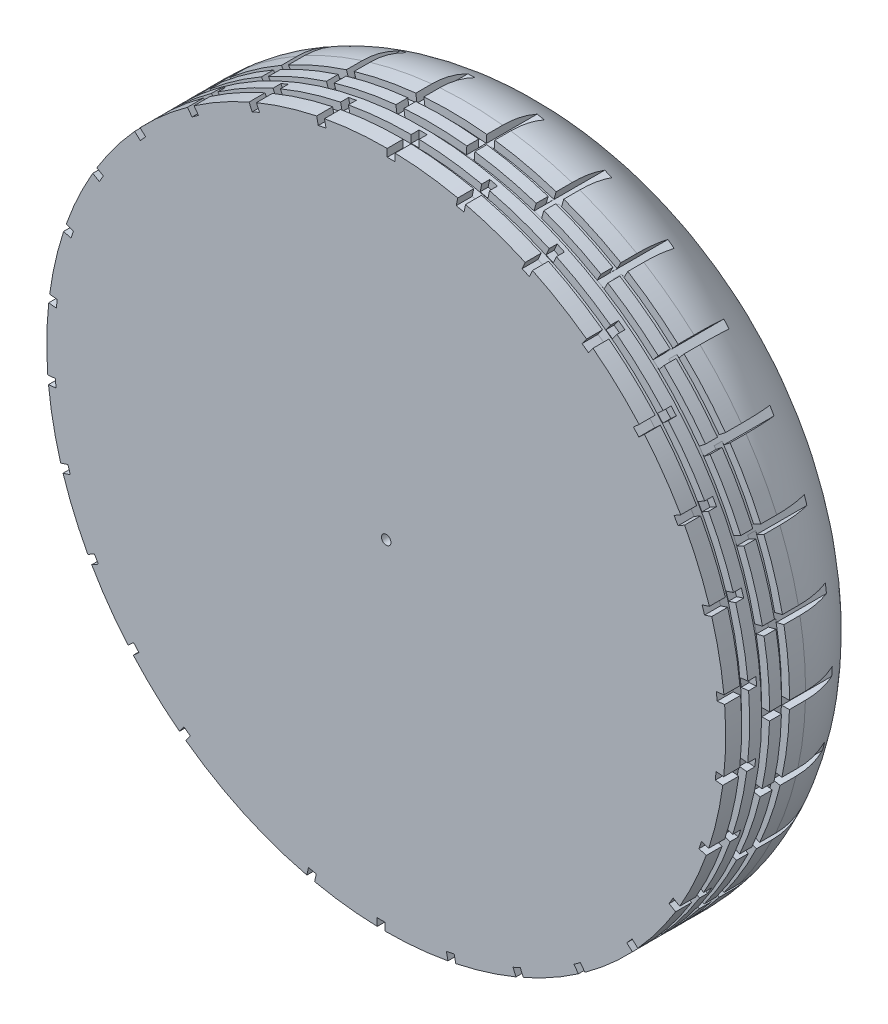
SolidWorks part; units mm, degrees
material "BUTYL"
ref_plane "Front Plane" through (0, 0, 0) normal (0, 0, 1) x (1, 0, 0)
ref_plane "Top Plane" through (0, 0, 0) normal (0, 1, 0) x (1, 0, 0)
ref_plane "Right Plane" through (0, 0, 0) normal (1, 0, 0) x (0, 0, -1)
sketch "Sketch1" plane through (0, 0, 0) normal (0, 0, 1) x (1, 0, 0)
  circle A0 centre (0, 0) radius 107.95
  dimension "D1" = 215.9
extrude "Boss-Extrude1" add sketch "Sketch1" along normal blind 25.4
sketch "Sketch3" plane through (0, 0, 0) normal (0, 1, 0) x (1, 0, 0)
  line L0 (107.95, 0) -> (-107.95, 0) construction
  line L1 (-107.95, 0) -> (107.95, 0)
  line L2 (0, 50.8) -> (0, 0) construction
  ellipse E0 centre (0, 0) end of major axis (107.95, 0) minor radius 50.8 (107.95, 0) -> (-107.95, 0) ccw
revolve "Revolve1" add sketch "Sketch3" angle 360 about L2 region at (0, 0, -21.5559)
sketch "Sketch5" plane through (0, 0, 25.4) normal (0, 0, 1) x (1, 0, 0)
  circle A0 centre (0, 0) radius 1.5
  dimension "D1" = 3
extrude "Cut-Extrude1" cut sketch "Sketch5" against normal blind 50.8
ref_plane "Plane1" through (0, 0, 12.7) normal (0, 0, 1) x (1, 0, 0)
sketch "Sketch6" plane through (0, 0, 12.7) normal (0, 0, 1) x (1, 0, 0)
  circle A0 centre (0, 0) radius 107.95
  circle A1 centre (0, 0) radius 105.41
  dimension "D1" = 210.82
extrude "Cut-Extrude2" cut sketch "Sketch6" against normal mid plane 2.54
pattern_linear "LPattern1" count 2 spacing 6.35 along (0, 0, 1) count 2 spacing 6.35 along (0, 0, -1) of "Cut-Extrude2" pattern seed only yes
sketch "Sketch9" plane through (0, 0, 12.7) normal (0, 0, 1) x (1, 0, 0)
  line L0 (25.2624, 105.0942) -> (24.7344, 102.6097)
  line L1 (0, 105.51) -> (0.3201, 105.51) construction
  line L2 (0.3201, 105.51) -> (2.8601, 105.51)
  line L3 (0.3201, 105.51) -> (0.3201, 108.05)
  line L4 (0.3201, 108.05) -> (2.8601, 108.05)
  line L5 (2.8601, 108.05) -> (2.8601, 105.51)
  line L6 (22.2499, 103.1378) -> (24.7344, 102.6097)
  line L7 (22.2499, 103.1378) -> (22.778, 105.6223)
  line L8 (22.778, 105.6223) -> (25.2624, 105.0942)
  line L9 (46.5607, 97.5453) -> (45.5276, 95.2249)
  line L10 (43.2072, 96.258) -> (45.5276, 95.2249)
  line L11 (43.2072, 96.258) -> (44.2403, 98.5784)
  line L12 (44.2403, 98.5784) -> (46.5607, 97.5453)
  line L13 (65.8241, 85.7332) -> (64.3311, 83.6783)
  line L14 (62.2762, 85.1712) -> (64.3311, 83.6783)
  line L15 (62.2762, 85.1712) -> (63.7692, 87.2261)
  line L16 (63.7692, 87.2261) -> (65.8241, 85.7332)
  line L17 (82.2106, 70.1741) -> (80.323, 68.4745)
  line L18 (78.6234, 70.3621) -> (80.323, 68.4745)
  line L19 (78.6234, 70.3621) -> (80.511, 72.0617)
  line L20 (80.511, 72.0617) -> (82.2106, 70.1741)
  line L21 (95.0041, 51.5481) -> (92.8044, 50.2781)
  line L22 (91.5344, 52.4778) -> (92.8044, 50.2781)
  line L23 (91.5344, 52.4778) -> (93.7341, 53.7478)
  line L24 (93.7341, 53.7478) -> (95.0041, 51.5481)
  line L25 (103.6455, 30.6692) -> (101.2298, 29.8843)
  line L26 (100.4449, 32.3) -> (101.2298, 29.8843)
  line L27 (100.4449, 32.3) -> (102.8606, 33.0849)
  line L28 (102.8606, 33.0849) -> (103.6455, 30.6692)
  line L29 (107.7571, 8.4499) -> (105.231, 8.1844)
  line L30 (104.9655, 10.7105) -> (105.231, 8.1844)
  line L31 (104.9655, 10.7105) -> (107.4916, 10.976)
  line L32 (107.4916, 10.976) -> (107.7571, 8.4499)
  line L33 (107.1591, -14.1387) -> (104.6331, -13.8732)
  line L34 (104.8986, -11.3471) -> (104.6331, -13.8732)
  line L35 (104.8986, -11.3471) -> (107.4246, -11.6126)
  line L36 (107.4246, -11.6126) -> (107.1591, -14.1387)
  line L37 (101.8778, -36.1094) -> (99.4622, -35.3245)
  line L38 (100.2471, -32.9088) -> (99.4622, -35.3245)
  line L39 (100.2471, -32.9088) -> (102.6628, -33.6937)
  line L40 (102.6628, -33.6937) -> (101.8778, -36.1094)
  line L41 (92.144, -56.5019) -> (89.9443, -55.2319)
  line L42 (91.2143, -53.0322) -> (89.9443, -55.2319)
  line L43 (91.2143, -53.0322) -> (93.414, -54.3022)
  line L44 (93.414, -54.3022) -> (92.144, -56.5019)
  line L45 (78.383, -74.425) -> (76.4954, -72.7254)
  line L46 (78.195, -70.8378) -> (76.4954, -72.7254)
  line L47 (78.195, -70.8378) -> (80.0826, -72.5374)
  line L48 (80.0826, -72.5374) -> (78.383, -74.425)
  line L49 (61.1963, -89.0954) -> (59.7034, -87.0405)
  line L50 (61.7583, -85.5475) -> (59.7034, -87.0405)
  line L51 (61.7583, -85.5475) -> (63.2512, -87.6024)
  line L52 (63.2512, -87.6024) -> (61.1963, -89.0954)
  line L53 (41.3351, -99.8719) -> (40.302, -97.5515)
  line L54 (42.6224, -96.5184) -> (40.302, -97.5515)
  line L55 (42.6224, -96.5184) -> (43.6555, -98.8388)
  line L56 (43.6555, -98.8388) -> (41.3351, -99.8719)
  line L57 (19.6673, -106.2835) -> (19.1392, -103.799)
  line L58 (21.6237, -103.2709) -> (19.1392, -103.799)
  line L59 (21.6237, -103.2709) -> (22.1518, -105.7554)
  line L60 (22.1518, -105.7554) -> (19.6673, -106.2835)
  line L61 (-2.8601, -108.05) -> (-2.8601, -105.51)
  line L62 (-0.3201, -105.51) -> (-2.8601, -105.51)
  line L63 (-0.3201, -105.51) -> (-0.3201, -108.05)
  line L64 (-0.3201, -108.05) -> (-2.8601, -108.05)
  line L65 (-25.2624, -105.0942) -> (-24.7344, -102.6097)
  line L66 (-22.2499, -103.1378) -> (-24.7344, -102.6097)
  line L67 (-22.2499, -103.1378) -> (-22.778, -105.6223)
  line L68 (-22.778, -105.6223) -> (-25.2624, -105.0942)
  line L69 (-46.5607, -97.5453) -> (-45.5276, -95.2249)
  line L70 (-43.2072, -96.258) -> (-45.5276, -95.2249)
  line L71 (-43.2072, -96.258) -> (-44.2403, -98.5784)
  line L72 (-44.2403, -98.5784) -> (-46.5607, -97.5453)
  line L73 (-65.8241, -85.7332) -> (-64.3311, -83.6783)
  line L74 (-62.2762, -85.1712) -> (-64.3311, -83.6783)
  line L75 (-62.2762, -85.1712) -> (-63.7692, -87.2261)
  line L76 (-63.7692, -87.2261) -> (-65.8241, -85.7332)
  line L77 (-82.2106, -70.1741) -> (-80.323, -68.4745)
  line L78 (-78.6234, -70.3621) -> (-80.323, -68.4745)
  line L79 (-78.6234, -70.3621) -> (-80.511, -72.0617)
  line L80 (-80.511, -72.0617) -> (-82.2106, -70.1741)
  line L81 (-95.0041, -51.5481) -> (-92.8044, -50.2781)
  line L82 (-91.5344, -52.4778) -> (-92.8044, -50.2781)
  line L83 (-91.5344, -52.4778) -> (-93.7341, -53.7478)
  line L84 (-93.7341, -53.7478) -> (-95.0041, -51.5481)
  line L85 (-103.6455, -30.6692) -> (-101.2298, -29.8843)
  line L86 (-100.4449, -32.3) -> (-101.2298, -29.8843)
  line L87 (-100.4449, -32.3) -> (-102.8606, -33.0849)
  line L88 (-102.8606, -33.0849) -> (-103.6455, -30.6692)
  line L89 (-107.7571, -8.4499) -> (-105.231, -8.1844)
  line L90 (-104.9655, -10.7105) -> (-105.231, -8.1844)
  line L91 (-104.9655, -10.7105) -> (-107.4916, -10.976)
  line L92 (-107.4916, -10.976) -> (-107.7571, -8.4499)
  line L93 (-107.1591, 14.1387) -> (-104.6331, 13.8732)
  line L94 (-104.8986, 11.3471) -> (-104.6331, 13.8732)
  line L95 (-104.8986, 11.3471) -> (-107.4246, 11.6126)
  line L96 (-107.4246, 11.6126) -> (-107.1591, 14.1387)
  line L97 (-101.8778, 36.1094) -> (-99.4622, 35.3245)
  line L98 (-100.2471, 32.9088) -> (-99.4622, 35.3245)
  line L99 (-100.2471, 32.9088) -> (-102.6628, 33.6937)
  line L100 (-102.6628, 33.6937) -> (-101.8778, 36.1094)
  line L101 (-92.144, 56.5019) -> (-89.9443, 55.2319)
  line L102 (-91.2143, 53.0322) -> (-89.9443, 55.2319)
  line L103 (-91.2143, 53.0322) -> (-93.414, 54.3022)
  line L104 (-93.414, 54.3022) -> (-92.144, 56.5019)
  line L105 (-78.383, 74.425) -> (-76.4954, 72.7254)
  line L106 (-78.195, 70.8378) -> (-76.4954, 72.7254)
  line L107 (-78.195, 70.8378) -> (-80.0826, 72.5374)
  line L108 (-80.0826, 72.5374) -> (-78.383, 74.425)
  line L109 (-61.1963, 89.0954) -> (-59.7034, 87.0405)
  line L110 (-61.7583, 85.5475) -> (-59.7034, 87.0405)
  line L111 (-61.7583, 85.5475) -> (-63.2512, 87.6024)
  line L112 (-63.2512, 87.6024) -> (-61.1963, 89.0954)
  line L113 (-41.3351, 99.8719) -> (-40.302, 97.5515)
  line L114 (-42.6224, 96.5184) -> (-40.302, 97.5515)
  line L115 (-42.6224, 96.5184) -> (-43.6555, 98.8388)
  line L116 (-43.6555, 98.8388) -> (-41.3351, 99.8719)
  line L117 (-19.6673, 106.2835) -> (-19.1392, 103.799)
  line L118 (-21.6237, 103.2709) -> (-19.1392, 103.799)
  line L119 (-21.6237, 103.2709) -> (-22.1518, 105.7554)
  line L120 (-22.1518, 105.7554) -> (-19.6673, 106.2835)
  circle A0 centre (0, 0) radius 107.95 construction
  point P125 (0, 0)
  dimension "D1" = 30
  dimension "D3" = 2.54
  dimension "D4" = 2.54
extrude "Cut-Extrude4" cut sketch "Sketch9" against normal blind 10.16 from surface contours L5 L2 L3 L4 | L117 L118 L119 L120 | L113 L114 L115 L116 | L109 L110 L111 L112 | L105 L106 L107 L108 | L101 L102 L103 L104 | L97 L98 L99 L100 | L93 L94 L95 L96 | L89 L90 L91 L92 | L85 L86 L87 L88 | L81 L82 L83 L84 | L77 L78 L79 L80 | L73 L74 L75 L76 | L65 L66 L67 L68 | L61 L62 L63 L64 | L57 L58 L59 L60 | L53 L54 L55 L56 | L49 L50 L51 L52 | L45 L46 L47 L48 | L41 L42 L43 L44 | L37 L38 L39 L40 | L33 L34 L35 L36 | L29 L30 L31 L32 | L21 L22 L23 L24 | L25 L26 L27 L28 | L17 L18 L19 L20 | L13 L14 L15 L16 | L9 L10 L11 L12 | L0 L6 L7 L8 starting at face at (1.5, 0, 25.4)
sketch "Sketch11" plane through (0, 0, 11.43) normal (0, 0, 1) x (1, 0, 0)
  line L0 (7.3106, 104.996) -> (11.4837, 104.7054) construction
  line L1 (34.0539, 103.7014) -> (33.0023, 100.0298)
  line L2 (7.3106, 104.996) -> (14.0314, 104.5281) construction
  line L3 (11.4837, 104.7054) -> (14.0314, 104.5281)
  line L4 (14.0314, 104.5281) -> (14.2966, 108.3381)
  line L5 (14.2966, 108.3381) -> (11.749, 108.5154)
  line L6 (11.749, 108.5154) -> (11.4837, 104.7054)
  line L7 (33.0023, 100.0298) -> (35.4574, 99.3266)
  line L8 (35.4574, 99.3266) -> (36.509, 102.9982)
  line L9 (36.509, 102.9982) -> (34.0539, 103.7014)
  line L10 (54.8705, 94.355) -> (53.0784, 90.9823)
  line L11 (53.0784, 90.9823) -> (55.3337, 89.7841)
  line L12 (55.3337, 89.7841) -> (57.1257, 93.1568)
  line L13 (57.1257, 93.1568) -> (54.8705, 94.355)
  line L14 (73.2889, 80.885) -> (70.8348, 77.9585)
  line L15 (70.8348, 77.9585) -> (72.7917, 76.3175)
  line L16 (72.7917, 76.3175) -> (75.2457, 79.244)
  line L17 (75.2457, 79.244) -> (73.2889, 80.885)
  line L18 (88.5043, 63.8798) -> (85.4954, 61.5276)
  line L19 (85.4954, 61.5276) -> (87.0683, 59.5156)
  line L20 (87.0683, 59.5156) -> (90.0772, 61.8678)
  line L21 (90.0772, 61.8678) -> (88.5043, 63.8798)
  line L22 (99.8516, 44.0828) -> (96.4194, 42.4075)
  line L23 (96.4194, 42.4075) -> (97.5396, 40.1125)
  line L24 (97.5396, 40.1125) -> (100.9718, 41.7878)
  line L25 (100.9718, 41.7878) -> (99.8516, 44.0828)
  line L26 (106.835, 22.3592) -> (103.1295, 21.4341)
  line L27 (103.1295, 21.4341) -> (103.748, 18.9563)
  line L28 (103.748, 18.9563) -> (107.4535, 19.8814)
  line L29 (107.4535, 19.8814) -> (106.835, 22.3592)
  line L30 (109.1491, -0.3417) -> (105.3322, -0.4761)
  line L31 (105.3322, -0.4761) -> (105.4221, -3.0283)
  line L32 (105.4221, -3.0283) -> (109.239, -2.8939)
  line L33 (109.239, -2.8939) -> (109.1491, -0.3417)
  line L34 (106.6929, -23.0276) -> (102.9315, -22.3655)
  line L35 (102.9315, -22.3655) -> (102.4888, -24.8807)
  line L36 (102.4888, -24.8807) -> (106.2502, -25.5427)
  line L37 (106.2502, -25.5427) -> (106.6929, -23.0276)
  line L38 (99.5737, -44.7071) -> (96.0321, -43.2774)
  line L39 (96.0321, -43.2774) -> (95.0762, -45.6456)
  line L40 (95.0762, -45.6456) -> (98.6177, -47.0752)
  line L41 (98.6177, -47.0752) -> (99.5737, -44.7071)
  line L42 (88.1026, -64.4327) -> (84.9357, -62.2979)
  line L43 (84.9357, -62.2979) -> (83.5083, -64.4155)
  line L44 (83.5083, -64.4155) -> (86.6752, -66.5503)
  line L45 (86.6752, -66.5503) -> (88.1026, -64.4327)
  line L46 (72.7811, -81.3422) -> (70.1272, -78.5957)
  line L47 (70.1272, -78.5957) -> (68.2907, -80.3703)
  line L48 (68.2907, -80.3703) -> (70.9445, -83.1168)
  line L49 (70.9445, -83.1168) -> (72.7811, -81.3422)
  line L50 (54.2786, -94.6967) -> (52.2538, -91.4584)
  line L51 (52.2538, -91.4584) -> (50.0884, -92.8124)
  line L52 (50.0884, -92.8124) -> (52.1133, -96.0507)
  line L53 (52.1133, -96.0507) -> (54.2786, -94.6967)
  line L54 (33.404, -103.9125) -> (32.0966, -100.324)
  line L55 (32.0966, -100.324) -> (29.6971, -101.1982)
  line L56 (29.6971, -101.1982) -> (31.0044, -104.7867)
  line L57 (31.0044, -104.7867) -> (33.404, -103.9125)
  line L58 (11.0694, -108.5869) -> (10.5367, -104.805)
  line L59 (10.5367, -104.805) -> (8.0079, -105.1612)
  line L60 (8.0079, -105.1612) -> (8.5405, -108.9431)
  line L61 (8.5405, -108.9431) -> (11.0694, -108.5869)
  line L62 (-11.749, -108.5154) -> (-11.4837, -104.7054)
  line L63 (-11.4837, -104.7054) -> (-14.0314, -104.5281)
  line L64 (-14.0314, -104.5281) -> (-14.2966, -108.3381)
  line L65 (-14.2966, -108.3381) -> (-11.749, -108.5154)
  line L66 (-34.0539, -103.7014) -> (-33.0023, -100.0298)
  line L67 (-33.0023, -100.0298) -> (-35.4574, -99.3266)
  line L68 (-35.4574, -99.3266) -> (-36.509, -102.9982)
  line L69 (-36.509, -102.9982) -> (-34.0539, -103.7014)
  line L70 (-54.8705, -94.355) -> (-53.0784, -90.9823)
  line L71 (-53.0784, -90.9823) -> (-55.3337, -89.7841)
  line L72 (-55.3337, -89.7841) -> (-57.1257, -93.1568)
  line L73 (-57.1257, -93.1568) -> (-54.8705, -94.355)
  line L74 (-73.2889, -80.885) -> (-70.8348, -77.9585)
  line L75 (-70.8348, -77.9585) -> (-72.7917, -76.3175)
  line L76 (-72.7917, -76.3175) -> (-75.2457, -79.244)
  line L77 (-75.2457, -79.244) -> (-73.2889, -80.885)
  line L78 (-88.5043, -63.8798) -> (-85.4954, -61.5276)
  line L79 (-85.4954, -61.5276) -> (-87.0683, -59.5156)
  line L80 (-87.0683, -59.5156) -> (-90.0772, -61.8678)
  line L81 (-90.0772, -61.8678) -> (-88.5043, -63.8798)
  line L82 (-99.8516, -44.0828) -> (-96.4194, -42.4075)
  line L83 (-96.4194, -42.4075) -> (-97.5396, -40.1125)
  line L84 (-97.5396, -40.1125) -> (-100.9718, -41.7878)
  line L85 (-100.9718, -41.7878) -> (-99.8516, -44.0828)
  line L86 (-106.835, -22.3592) -> (-103.1295, -21.4341)
  line L87 (-103.1295, -21.4341) -> (-103.748, -18.9563)
  line L88 (-103.748, -18.9563) -> (-107.4535, -19.8814)
  line L89 (-107.4535, -19.8814) -> (-106.835, -22.3592)
  line L90 (-109.1491, 0.3417) -> (-105.3322, 0.4761)
  line L91 (-105.3322, 0.4761) -> (-105.4221, 3.0283)
  line L92 (-105.4221, 3.0283) -> (-109.239, 2.8939)
  line L93 (-109.239, 2.8939) -> (-109.1491, 0.3417)
  line L94 (-106.6929, 23.0276) -> (-102.9315, 22.3655)
  line L95 (-102.9315, 22.3655) -> (-102.4888, 24.8807)
  line L96 (-102.4888, 24.8807) -> (-106.2502, 25.5427)
  line L97 (-106.2502, 25.5427) -> (-106.6929, 23.0276)
  line L98 (-99.5737, 44.7071) -> (-96.0321, 43.2774)
  line L99 (-96.0321, 43.2774) -> (-95.0762, 45.6456)
  line L100 (-95.0762, 45.6456) -> (-98.6177, 47.0752)
  line L101 (-98.6177, 47.0752) -> (-99.5737, 44.7071)
  line L102 (-88.1026, 64.4327) -> (-84.9357, 62.2979)
  line L103 (-84.9357, 62.2979) -> (-83.5083, 64.4155)
  line L104 (-83.5083, 64.4155) -> (-86.6752, 66.5503)
  line L105 (-86.6752, 66.5503) -> (-88.1026, 64.4327)
  line L106 (-72.7811, 81.3422) -> (-70.1272, 78.5957)
  line L107 (-70.1272, 78.5957) -> (-68.2907, 80.3703)
  line L108 (-68.2907, 80.3703) -> (-70.9445, 83.1168)
  line L109 (-70.9445, 83.1168) -> (-72.7811, 81.3422)
  line L110 (-54.2786, 94.6967) -> (-52.2538, 91.4584)
  line L111 (-52.2538, 91.4584) -> (-50.0884, 92.8124)
  line L112 (-50.0884, 92.8124) -> (-52.1133, 96.0507)
  line L113 (-52.1133, 96.0507) -> (-54.2786, 94.6967)
  line L114 (-33.404, 103.9125) -> (-32.0966, 100.324)
  line L115 (-32.0966, 100.324) -> (-29.6971, 101.1982)
  line L116 (-29.6971, 101.1982) -> (-31.0044, 104.7867)
  line L117 (-31.0044, 104.7867) -> (-33.404, 103.9125)
  line L118 (-11.0694, 108.5869) -> (-10.5367, 104.805)
  line L119 (-10.5367, 104.805) -> (-8.0079, 105.1612)
  line L120 (-8.0079, 105.1612) -> (-8.5405, 108.9431)
  line L121 (-8.5405, 108.9431) -> (-11.0694, 108.5869)
  circle A1 centre (0, 0) radius 107.95 construction
  point P125 (0, 0)
  dimension "D1" = 30
  dimension "D4" = 3.81
extrude "Cut-Extrude5" cut sketch "Sketch11" against normal blind 58.42
